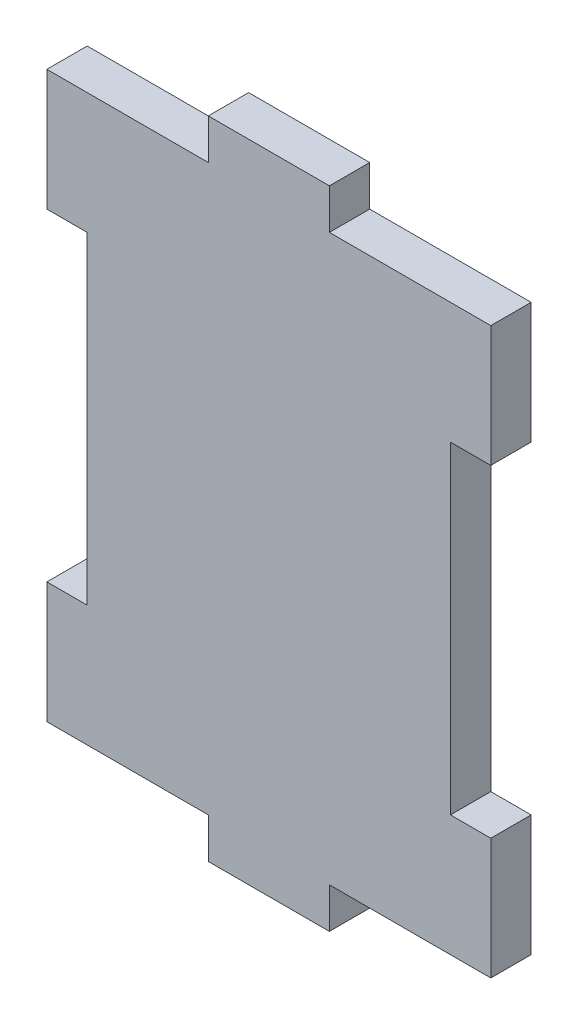
SolidWorks part; units mm, degrees
material "Acrylic (Medium-high impact)"
ref_plane "Front Plane" through (0, 0, 0) normal (0, 0, 1) x (1, 0, 0)
ref_plane "Top Plane" through (0, 0, 0) normal (0, 1, 0) x (1, 0, 0)
ref_plane "Right Plane" through (0, 0, 0) normal (1, 0, 0) x (0, 0, -1)
sketch "Sketch2" plane through (0, 0, 0) normal (0, 0, 1) x (1, 0, 0)
  line L0 (-7.5, 40) -> (7.5, 40)
  line L1 (7.5, 40) -> (7.5, 35)
  line L2 (7.5, 35) -> (27.5, 35)
  line L3 (27.5, 35) -> (27.5, -35)
  line L4 (0, 0) -> (27.5, 0) construction
  line L5 (0, -40) -> (0, 40) construction
  line L6 (-27.5, 35) -> (-27.5, -35)
  line L7 (-7.5, 35) -> (-27.5, 35)
  line L8 (-7.5, 40) -> (-7.5, 35)
  line L9 (-7.5, -40) -> (-7.5, -35)
  line L10 (-7.5, -35) -> (-27.5, -35)
  line L11 (7.5, -35) -> (27.5, -35)
  line L12 (7.5, -40) -> (7.5, -35)
  line L13 (-7.5, -40) -> (7.5, -40)
  point P17 (-27.5, 0)
  dimension "D1" = 5
  dimension "D2" = 27.5
  dimension "D3" = 7.5
  dimension "D4" = 40
extrude "Boss-Extrude2" add sketch "Sketch2" along normal blind 5
sketch "Sketch3" plane through (0, 0, 5) normal (0, 0, 1) x (1, 0, 0)
  line L0 (0, 0) -> (-27.5, 0) construction
  line L1 (-27.5, 35) -> (-27.5, -35) construction
  line L3 (-22.5, -20) -> (-27.5, -20)
  line L4 (-22.5, -20) -> (-22.5, 20)
  line L5 (-22.5, 20) -> (-27.5, 20)
  line L6 (-27.5, -20) -> (-27.5, 20)
  line L7 (-22.5, -20) -> (-27.5, 20) construction
  line L8 (-22.5, 20) -> (-27.5, -20) construction
  point P5 (-25, 0)
  point P8 (-27.5, 0)
  dimension "D1" = 40
  dimension "D2" = 5
extrude "Cut-Extrude1" cut sketch "Sketch3" against normal blind 5
mirror "Mirror1" about plane through (0, 0, 0) normal (1, 0, 0) of "Cut-Extrude1"
